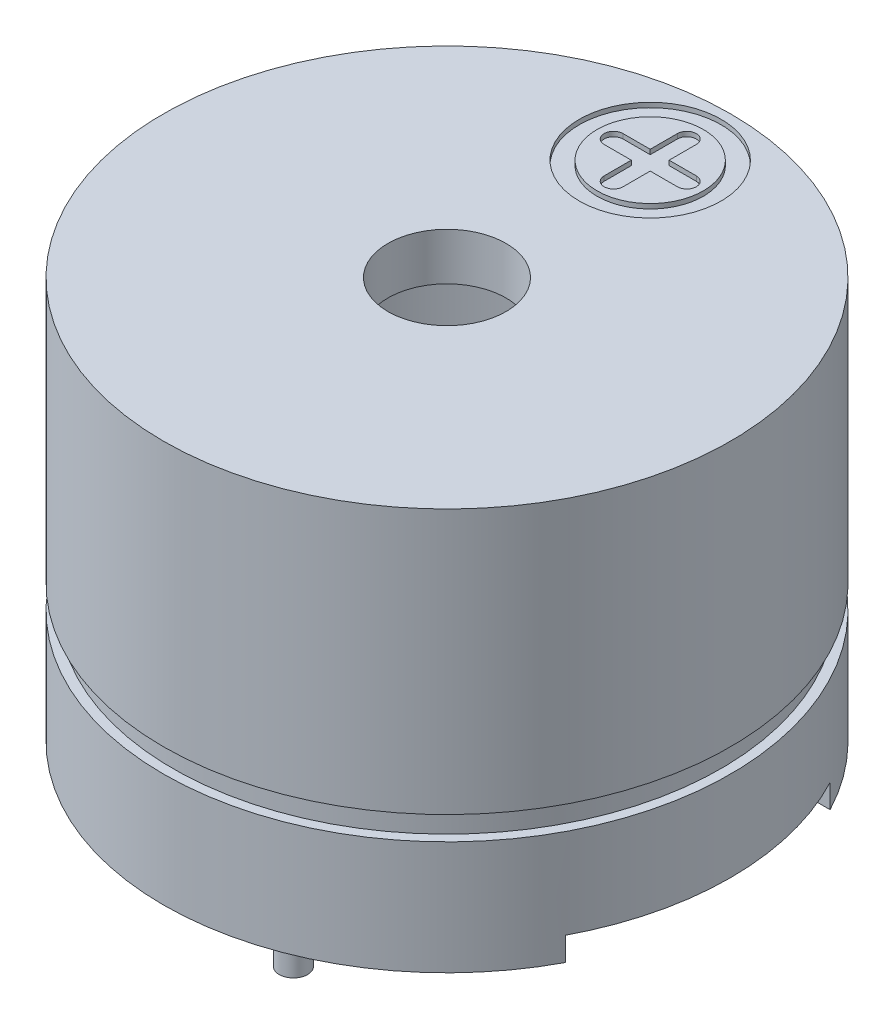
SolidWorks part; units mm, degrees
ref_plane "Front Plane" through (0, 0, 0) normal (0, 0, 1) x (1, 0, 0)
ref_plane "Top Plane" through (0, 0, 0) normal (0, 1, 0) x (1, 0, 0)
ref_plane "Right Plane" through (0, 0, 0) normal (1, 0, 0) x (0, 0, -1)
sketch "Sketch1" plane through (0, 0, 0) normal (0, 1, 0) x (1, 0, 0)
  circle A0 centre (0, 0) radius 6
  circle A1 centre (0, 0) radius 5
  circle A2 centre (0, 0) radius 1.25
  circle A3 centre (0, 0) radius 3
  dimension "D1" = 12
  dimension "D2" = 1
  dimension "D3" = 2.5
  dimension "D4" = 6
extrude "Boss-Extrude1" add sketch "Sketch1" along normal blind 8.5 contours A0 A1 | A1 | A3 A2 region at (-5.8303, 0, 0) region at (-4.8586, 0, 0) region at (-2.9151, 0, 0)
extrude "Cut-Extrude1" cut sketch "Sketch1<3>" along normal offset from surface (7.5 mm away) 1 contours A1 | A3 A2 region at (-4.8586, 0, 0) region at (-2.9151, 0, 0) up to face at (0, 8.5, 6)
sketch "Sketch1<3>" plane through (0, 0, 0) normal (0, 1, 0) x (1, 0, 0) same geometry as "Sketch1"
sketch "Sketch2" plane through (0, 0, 0) normal (1, 0, 0) x (0, 0, -1)
  line L1 (-2.8, 0) -> (2.8, 0)
  line L2 (-2.8, 0) -> (-2.8, 0.5)
  line L3 (-2.8, 0.5) -> (2.8, 0.5)
  line L4 (2.8, 0) -> (2.8, 0.5)
  point P4 (0, 0)
  dimension "D1" = 0.5
  dimension "D2" = 5.6
extrude "Cut-Extrude2" cut sketch "Sketch2" against normal through all both and the other way through all
extrude "Boss-Extrude2" add sketch "Sketch1<4>" along normal blind 2 from offset 1 separate body contours A1 A3 region at (-4.8586, 0, 0)
sketch "Sketch1<4>" plane through (0, 0, 0) normal (0, 1, 0) x (1, 0, 0) same geometry as "Sketch1"
sketch "Sketch3" plane through (0, 1, 0) normal (0, -1, 0) x (1, 0, 0)
  line L0 (0, -1000) -> (0, 49000) construction
  line L1 (-1000, 0) -> (49000, 0) construction
  line L2 (3.375, 1.125) -> (4.2, 1.125)
  line L3 (3.375, -1.125) -> (4.2, -1.125)
  line L4 (4.4, 1.325) -> (4.4, 2.3749)
  line L5 (4.4, -1.325) -> (4.4, -2.3749)
  line L6 (-4.4, -1.325) -> (-4.4, -2.3749)
  line L7 (-4.4, 1.325) -> (-4.4, 2.3749)
  line L8 (-3.375, -1.125) -> (-4.2, -1.125)
  line L9 (-3.375, 1.125) -> (-4.2, 1.125)
  circle A0 centre (0, 0) radius 5 construction
  arc A1 (4.4, 2.3749) -> (-4.4, 2.3749) centre (0, 0) ccw
  arc A2 (3.375, 1.125) -> (3.375, -1.125) centre (3.375, 0) ccw
  arc A3 (4.2, -1.125) -> (4.4, -1.325) centre (4.2, -1.325) cw
  arc A4 (4.2, 1.125) -> (4.4, 1.325) centre (4.2, 1.325) ccw
  arc A5 (-4.2, 1.125) -> (-4.4, 1.325) centre (-4.2, 1.325) cw
  arc A6 (-4.2, -1.125) -> (-4.4, -1.325) centre (-4.2, -1.325) ccw
  arc A7 (-3.375, 1.125) -> (-3.375, -1.125) centre (-3.375, 0) cw
  arc A8 (-4.4, -2.3749) -> (4.4, -2.3749) centre (0, 0) ccw
  dimension "D1" = 4.5
  dimension "D4" = 0.2
  dimension "D2" = 2.25
  dimension "D3" = 8.8
extrude "Boss-Extrude3" add sketch "Sketch3" along normal blind 0.25 separate body
sketch "Sketch4" plane through (0, 0.75, 0) normal (0, -1, 0) x (1, 0, 0)
  line L0 (-3.25, 3.7997) -> (-3.25, 1.118)
  line L1 (-3.25, -1.118) -> (-3.25, -3.7997)
  line L2 (0, -1000) -> (0, 49000) construction
  line L3 (3.25, -1.118) -> (3.25, -3.7997)
  line L4 (3.25, 3.7997) -> (3.25, 1.118)
  line L5 (-1000, 0) -> (49000, 0) construction
  line L8 (3.375, 1.125) -> (4.2, 1.125)
  line L9 (4.4, 1.325) -> (4.4, 2.3749)
  line L10 (-4.4, 2.3749) -> (-4.4, 1.325)
  line L11 (-4.2, 1.125) -> (-3.375, 1.125)
  line L12 (-3.375, -1.125) -> (-4.2, -1.125)
  line L13 (-4.4, -1.325) -> (-4.4, -2.3749)
  line L14 (4.4, -2.3749) -> (4.4, -1.325)
  line L15 (4.2, -1.125) -> (3.375, -1.125)
  circle A0 centre (0, 3.25) radius 0.3
  circle A1 centre (0, -3.25) radius 0.3
  arc A2 (3.375, 1.125) -> (3.375, -1.125) centre (3.375, 0) ccw construction
  arc A3 (3.25, 1.118) -> (3.25, -1.118) centre (3.375, 0) ccw
  arc A4 (-3.375, -1.125) -> (-3.375, 1.125) centre (-3.375, 0) ccw construction
  arc A5 (-3.25, -1.118) -> (-3.25, 1.118) centre (-3.375, 0) ccw
  arc A8 (3.375, 1.125) -> (3.375, -1.125) centre (3.375, 0) ccw
  arc A9 (4.2, 1.125) -> (4.4, 1.325) centre (4.2, 1.325) ccw
  arc A10 (4.4, 2.3749) -> (-4.4, 2.3749) centre (0, 0) ccw
  arc A11 (-4.4, 1.325) -> (-4.2, 1.125) centre (-4.2, 1.325) ccw
  arc A12 (-3.375, -1.125) -> (-3.375, 1.125) centre (-3.375, 0) ccw
  arc A13 (-4.2, -1.125) -> (-4.4, -1.325) centre (-4.2, -1.325) ccw
  arc A14 (-4.4, -2.3749) -> (4.4, -2.3749) centre (0, 0) ccw
  arc A15 (4.4, -1.325) -> (4.2, -1.125) centre (4.2, -1.325) ccw
  arc A18 (3.25, 3.7997) -> (-3.25, 3.7997) centre (0, 0) ccw
  arc A22 (-3.25, -3.7997) -> (3.25, -3.7997) centre (0, 0) ccw
  point P46 (-3.25, 1.118)
  point P47 (-3.25, -1.118)
  point P48 (3.25, -1.118)
  point P49 (3.25, 1.118)
  dimension "D3" = 0.6
  dimension "D2" = 6.5
  dimension "D4" = 6.5
  dimension "D1" = 0
extrude "Boss-Extrude4" add sketch "Sketch4" along normal blind 0.25 separate body
sketch "Sketch5" plane through (0, 0.5, 0) normal (0, -1, 0) x (1, 0, 0)
  line L0 (-2, -999.974) -> (-2, 49000.026) construction
  line L1 (-1000, 0) -> (49000, 0) construction
  line L2 (-2.9, -2.5) -> (-1.1, -2.5) construction
  line L3 (-2, -1.6) -> (-2, -3.4) construction
  line L4 (-2, 3.4) -> (-2, 1.6) construction
  line L5 (-2.9, -2.7) -> (-2.2, -2.7)
  line L6 (-2.2, -1.6) -> (-2.2, -2.3)
  line L7 (-2.2, 3.4) -> (-2.2, 1.6)
  line L8 (-2.9, -2.3) -> (-2.2, -2.3)
  line L9 (-1.8, -1.6) -> (-1.8, -2.3)
  line L10 (-1.8, 3.4) -> (-1.8, 1.6)
  line L11 (-1.8, -2.3) -> (-1.1, -2.3)
  line L13 (-2.2, -2.7) -> (-2.2, -3.4)
  line L14 (-2.2, -1.6) -> (-2.2, -3.4) construction
  line L15 (-1.8, -2.7) -> (-1.8, -3.4)
  line L17 (-1.8, -2.7) -> (-1.1, -2.7)
  line L18 (-2.9, -2.7) -> (-1.1, -2.7) construction
  circle A0 centre (0, 3.25) radius 0.9
  circle A1 centre (0, -3.25) radius 0.9
  circle A2 centre (0, 3.25) radius 0.3 construction
  circle A3 centre (0, 3.25) radius 0.3
  circle A4 centre (0, -3.25) radius 0.3 construction
  circle A5 centre (0, -3.25) radius 0.3
  arc A6 (-2.9, -2.7) -> (-2.9, -2.3) centre (-2.9, -2.5) cw
  arc A7 (-1.1, -2.7) -> (-1.1, -2.3) centre (-1.1, -2.5) ccw
  arc A8 (-2.2, -1.6) -> (-1.8, -1.6) centre (-2, -1.6) cw
  arc A9 (-2.2, -3.4) -> (-1.8, -3.4) centre (-2, -3.4) ccw
  arc A10 (-2.2, 3.4) -> (-1.8, 3.4) centre (-2, 3.4) cw
  arc A11 (-2.2, 1.6) -> (-1.8, 1.6) centre (-2, 1.6) ccw
  point P23 (0, 0)
  point P24 (0, 0)
  point P25 (0, 0)
  point P40 (-1.6102, 1.2608)
  point P42 (-2.2, 2.5)
  point P44 (-2.2456, 3.4)
  dimension "D1" = 1.8
  dimension "D2" = 1.8
  dimension "D5" = 2.5
  dimension "D3" = 0.4
  dimension "D4" = 2
extrude "Boss-Extrude5" add sketch "Sketch5" along normal blind 0.05
sketch "Sketch6" plane through (0, 0, 0) normal (1, 0, 0) x (0, 0, -1)
  line L0 (0, -1000) -> (0, 49000) construction
  line L1 (6, 0) -> (6, 8.5) construction
  line L2 (5.8, 2.9) -> (7.2237, 2.9)
  line L3 (5.8, 2.9) -> (5.8, 2.4)
  line L4 (5.8, 2.4) -> (7.2237, 2.4)
  line L5 (7.2237, 2.9) -> (7.2237, 2.4)
  dimension "D1" = 0.5
  dimension "D2" = 2.4
  dimension "D3" = 0.2
revolve "Cut-Revolve1" cut sketch "Sketch6" angle 360 about L0
sketch "Sketch7" plane through (0, 0.75, 0) normal (0, -1, 0) x (1, 0, 0)
  circle A0 centre (0, 3.25) radius 0.3 construction
  circle A1 centre (0, 3.25) radius 0.3
  circle A2 centre (0, -3.25) radius 0.3 construction
  circle A3 centre (0, -3.25) radius 0.3
extrude "Boss-Extrude7" add sketch "Sketch7" along normal offset from surface (3.25 mm away) 2.5 separate body up to plane "Top Plane" offset beyond the face yes
sketch "Sketch8" plane through (0, 8.5, 0) normal (0, 1, 0) x (1, 0, 0)
  line L0 (0, -1000) -> (0, 49000) construction
  line L1 (-0.775, 4.5) -> (-0.2, 4.5)
  line L2 (-0.775, 4.1) -> (-0.2, 4.1)
  line L3 (-1000, 4.3) -> (49000, 4.3) construction
  line L4 (-0.2, 4.5) -> (0, 4.3) construction
  line L5 (0.2, 5.075) -> (0.2, 4.5)
  line L6 (-0.2, 5.075) -> (-0.2, 4.5)
  line L7 (0.775, 4.1) -> (0.2, 4.1)
  line L8 (0.775, 4.5) -> (0.2, 4.5)
  line L9 (-0.2, 3.525) -> (-0.2, 4.1)
  line L10 (0.2, 3.525) -> (0.2, 4.1)
  line L11 (0, 4.3) -> (-0.2, 4.5) construction
  line L12 (0, 4.3) -> (0.2, 4.5) construction
  circle A0 centre (0, 4.3) radius 1.5
  circle A1 centre (0, 4.3) radius 1.125
  arc A2 (-0.775, 4.1) -> (-0.775, 4.5) centre (-0.775, 4.3) cw
  arc A3 (-0.2, 5.075) -> (0.2, 5.075) centre (0, 5.075) cw
  arc A4 (0.775, 4.5) -> (0.775, 4.1) centre (0.775, 4.3) cw
  arc A5 (0.2, 3.525) -> (-0.2, 3.525) centre (0, 3.525) cw
  point P10 (0, 0)
  point P13 (0, 0)
  dimension "D1" = 3
  dimension "D2" = 2.25
  dimension "D4" = 0.2
  dimension "D6" = 0.15
  dimension "D3" = 4.3
  dimension "D5" = 45
  dimension "D8" = 90
  dimension "D9" = 0.2828
  dimension "D7" = 4
extrude "Cut-Extrude3" cut sketch "Sketch8" against normal blind 0.1 contours A5 L10 L7 A4 L8 L5 A3 L6 L1 A2 L2 L9 | A0 A1 region at (0, 8.5, -4.3) region at (-1.4576, 8.5, -4.3)
